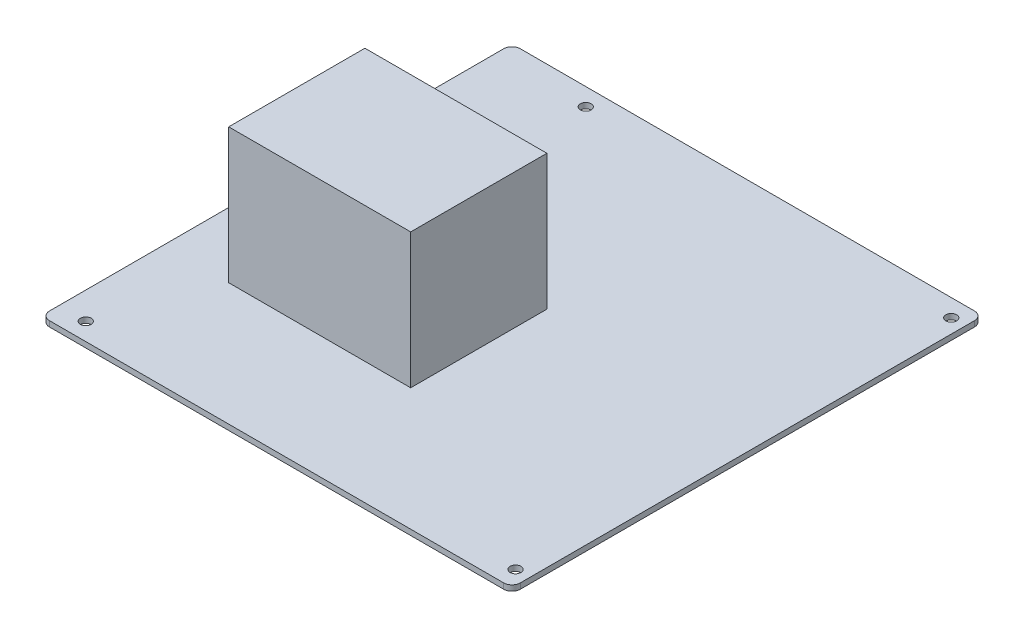
SolidWorks part; units mm, degrees
ref_plane "Front" through (0, 0, 0) normal (0, 0, 1) x (1, 0, 0)
ref_plane "Top" through (0, 0, 0) normal (0, 1, 0) x (1, 0, 0)
ref_plane "Right" through (0, 0, 0) normal (1, 0, 0) x (0, 0, -1)
sketch "Sketch1" plane through (0, 0, 0) normal (0, 1, 0) x (1, 0, 0)
  line L1 (85.09, 85.09) -> (-85.09, 85.09)
  line L2 (85.09, 85.09) -> (85.09, -85.09)
  line L3 (85.09, -85.09) -> (-85.09, -85.09)
  line L4 (-85.09, 85.09) -> (-85.09, -85.09)
  line L5 (85.09, 85.09) -> (-85.09, -85.09) construction
  line L6 (85.09, -85.09) -> (-85.09, 85.09) construction
  point P0 (0, 0)
  dimension "D1" = 170.18
  dimension "D2" = 170.18
extrude "Boss-Extrude1" add sketch "Sketch1" along normal blind 2
sketch "Sketch2" plane through (0, 2, 0) normal (0, 1, 0) x (1, 0, 0)
  line L1 (-61.5363, 8.3754) -> (4.2276, 8.3754)
  line L2 (-61.5363, 8.3754) -> (-61.5363, -40.8428)
  line L3 (-61.5363, -40.8428) -> (4.2276, -40.8428)
  line L4 (4.2276, 8.3754) -> (4.2276, -40.8428)
  line L5 (-61.5363, 8.3754) -> (4.2276, -40.8428) construction
  line L6 (-61.5363, -40.8428) -> (4.2276, 8.3754) construction
  point P0 (-28.6544, -16.2337)
extrude "Boss-Extrude2" add sketch "Sketch2" along normal blind 48.8
fillet "Fillet1" radius 3 4 edges at (-85.09, 1, -85.09) (85.09, 1, -85.09) (85.09, 1, 85.09) (-85.09, 1, 85.09)
hole_wizard "Ø3.9 (3.9) Diameter Hole1" positions "Sketch3" profile "Sketch4" hole size "Ø3.9" standard "ANSI Metric"
sketch "Sketch3" plane through (0, 2, 0) normal (0, 1, 0) x (1, 0, 0)
  line L0 (-82.09, -85.09) -> (82.09, -85.09) construction
  line L1 (85.09, -82.09) -> (85.09, 82.09) construction
  line L3 (-52.07, 78.74) -> (80.01, 78.74) construction
  point P0 (-75.29, -78.74)
  point P2 (80.01, -78.74)
  point P4 (80.01, 78.74)
  point P6 (-52.07, 78.74)
  dimension "D1" = 6.35
  dimension "D2" = 6.35
  dimension "D3" = 5.08
  dimension "D4" = 5.08
  dimension "D5" = 157.48
  dimension "D6" = 132.08
  dimension "D7" = 155.3
sketch "Sketch4" plane through (-75.29, 2, 78.74) normal (1, 0, 0) x (0, 0, 1)
  line L0 (0, 0) -> (0, 19.9217)
  line L1 (0, 19.9217) -> (1.95, 18.75)
  line L2 (1.95, 18.75) -> (1.95, 0)
  line L5 (1.95, 0) -> (0, 0)
  line L10 (0, 19.9217) -> (-1.95, 18.75) construction
  line L11 (0, -6.35) -> (0, 107.95) construction
  dimension "Hole Dia." = 3.9
  dimension "Hole Depth" = 18.75
  dimension "Drill Angle" = 118
